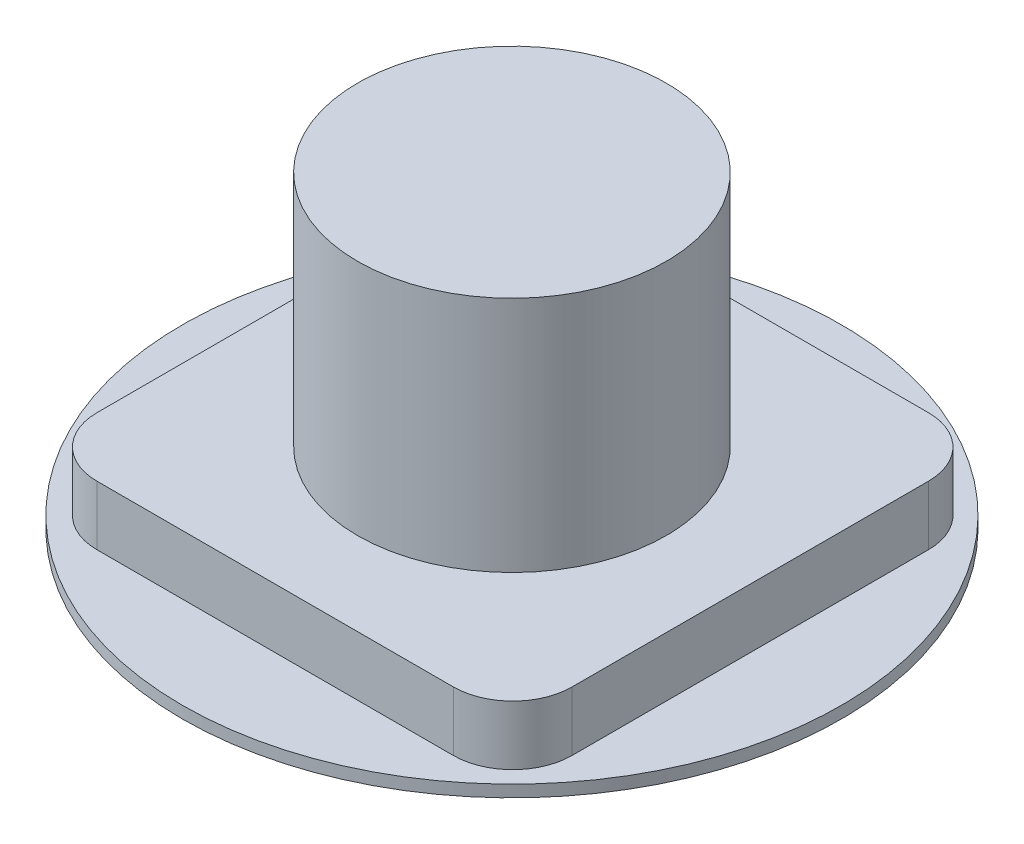
SolidWorks part; units mm, degrees
ref_plane "Front Plane" through (0, 0, 0) normal (0, 0, 1) x (1, 0, 0)
ref_plane "Top Plane" through (0, 0, 0) normal (0, 1, 0) x (1, 0, 0)
ref_plane "Right Plane" through (0, 0, 0) normal (1, 0, 0) x (0, 0, -1)
sketch "Sketch1" plane through (0, 0, 0) normal (0, 1, 0) x (1, 0, 0)
  circle A0 centre (0, 0) radius 277.5
extrude "Boss-Extrude1" add sketch "Sketch1" along normal blind 10
sketch "Sketch2" plane through (0, 10, 0) normal (0, 1, 0) x (1, 0, 0)
  line L1 (-199.3488, 200) -> (200.6512, 200)
  line L2 (-199.3488, 200) -> (-199.3488, -200)
  line L3 (-199.3488, -200) -> (200.6512, -200)
  line L4 (200.6512, 200) -> (200.6512, -200)
  line L5 (-199.3488, 200) -> (200.6512, -200) construction
  line L6 (-199.3488, -200) -> (200.6512, 200) construction
  point P0 (4.4291, 3.7779)
  dimension "D1" = 400
  dimension "D2" = 400
  dimension "D3" = 400
extrude "Boss-Extrude2" add sketch "Sketch2" along normal blind 50
fillet "Fillet1" radius 50 4 edges at (-199.3488, 35, -200) (200.6512, 35, -200) (200.6512, 35, 200) (-199.3488, 35, 200)
sketch "Sketch3" plane through (0, 60, 0) normal (0, 1, 0) x (1, 0, 0)
  circle A0 centre (0, 0) radius 130
extrude "Boss-Extrude3" add sketch "Sketch3" along normal blind 200
